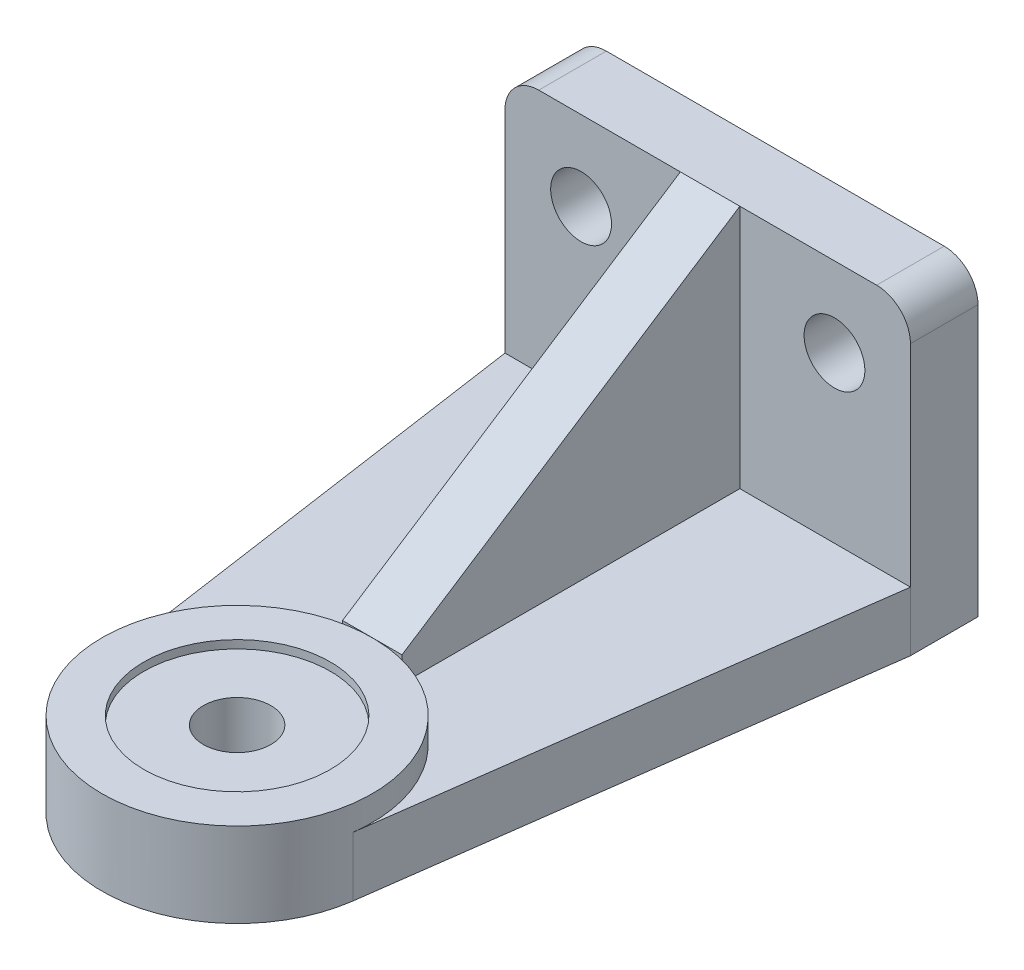
SolidWorks part; units mm, degrees
material "7075-T6 (SN)"
ref_plane "Front Plane" through (0, 0, 0) normal (0, 0, 1) x (1, 0, 0)
ref_plane "Top Plane" through (0, 0, 0) normal (0, 1, 0) x (1, 0, 0)
ref_plane "Right Plane" through (0, 0, 0) normal (1, 0, 0) x (0, 0, -1)
ref_axis "X-axis" through (-88.99, 0, 0) along (1, 0, 0)
ref_axis "Y-axis" through (0, 55, 0) along (0, -1, 0)
ref_axis "Z-axis" through (0, 0, -88.99) along (0, 0, 1)
sketch "Sketch1" plane through (0, 0, 0) normal (0, 1, 0) x (1, 0, 0)
  line L0 (-25.1373, -3.6439) -> (-38.5523, 88.9)
  line L1 (-38.5523, 88.9) -> (37.6477, 88.9)
  line L2 (37.6477, 88.9) -> (25.1711, -3.4024)
  arc A0 (-25.1373, -3.6439) -> (25.1711, -3.4024) centre (0, 0) ccw
  dimension "D1" = 50.8
  dimension "D2" = 88.9
  dimension "D3" = 76.2
extrude "Boss-Extrude1" add sketch "Sketch1" along normal blind 15.875
sketch "Sketch2" plane through (0, 15.875, 0) normal (0, 1, 0) x (1, 0, 0)
  line L0 (-38.5523, 88.9) -> (37.6477, 88.9)
  line L1 (37.6477, 88.9) -> (25.1711, -3.4024)
  line L2 (-25.1373, -3.6439) -> (-38.5523, 88.9)
  arc A0 (25.1711, -3.4024) -> (-25.1373, -3.6439) centre (0, 0) ccw
extrude "Cut-Extrude1" cut sketch "Sketch2" against normal blind 4.699
sketch "Sketch4" plane through (0, 0, -88.9) normal (0, 0, -1) x (-1, 0, 0)
  line L1 (-37.6477, 0) -> (38.5523, 0)
  line L2 (-37.6477, 0) -> (-37.6477, 57.15)
  line L3 (-37.6477, 57.15) -> (38.5523, 57.15)
  line L4 (38.5523, 0) -> (38.5523, 57.15)
  dimension "D1" = 76.2
  dimension "D2" = 57.15
extrude "Boss-Extrude2" add sketch "Sketch4" along normal blind 12.7
sketch "Sketch5" plane through (0, 0, 0) normal (1, 0, 0) x (0, 0, -1)
  line L0 (88.9, 57.15) -> (25.4, 15.875)
  line L1 (25.4, 15.875) -> (25.4, 11.176)
  line L2 (25.4, 11.176) -> (88.9, 11.176)
  line L3 (88.9, 11.176) -> (88.9, 57.15)
extrude "Boss-Extrude4" add sketch "Sketch5" along normal mid plane 11.176 separate body
hole_wizard "CBORE for 1/4 Binding Head Machine Screw1" positions "Sketch6" profile "Sketch7" counterbore size "1/4" standard "ANSI Inch" end condition through all
sketch "Sketch6" plane through (0, 15.875, 0) normal (0, 1, 0) x (1, 0, 0)
  point P0 (0, 0)
sketch "Sketch7" plane through (0, 15.875, 0) normal (1, 0, 0) x (0, 0, 1)
  line L0 (0, 0) -> (0, 15.875)
  line L1 (0, 15.875) -> (6.35, 15.875)
  line L3 (6.35, 15.875) -> (6.35, 1.524)
  line L4 (6.35, 1.524) -> (17.526, 1.524)
  line L5 (17.526, 1.524) -> (17.526, 0)
  line L7 (17.526, 0) -> (0, 0)
  line L11 (0, -6.35) -> (0, 107.95) construction
  dimension "Thru Hole Dia." = 12.7
  dimension "Thru Hole Depth" = 15.875
  dimension "C'Bore Dia." = 35.052
  dimension "C'Bore Depth" = 1.524
hole_wizard "1/4 (0.45) Diameter Hole1" positions "Sketch8" profile "Sketch9" hole size "1/4" standard "ANSI Inch" end condition through all
sketch "Sketch8" plane through (0, 0, -88.9) normal (0, 0, 1) x (1, 0, 0)
  line L0 (-24.2521, 42.164) -> (23.3729, 42.164)
  line L2 (-38.5523, 11.176) -> (-38.5523, 57.15) construction
  line L3 (-38.5523, 57.15) -> (37.6477, 57.15) construction
  point P0 (-24.2521, 42.164)
  point P2 (23.3729, 42.164)
  dimension "D1" = 14.3002
  dimension "D2" = 47.625
  dimension "D3" = 14.986
sketch "Sketch9" plane through (-24.2521, 42.164, -88.9) normal (1, 0, 0) x (0, -1, 0)
  line L0 (0, 0) -> (0, 12.7)
  line L1 (0, 12.7) -> (5.715, 12.7)
  line L2 (5.715, 12.7) -> (5.715, 0)
  line L5 (5.715, 0) -> (0, 0)
  line L11 (0, -6.35) -> (0, 107.95) construction
  dimension "Thru Hole Dia." = 11.43
  dimension "Thru Hole Depth" = 12.7
fillet "Fillet1" radius 6.35 2 edges at (37.6477, 57.15, -95.25) (-38.5523, 57.15, -95.25)
